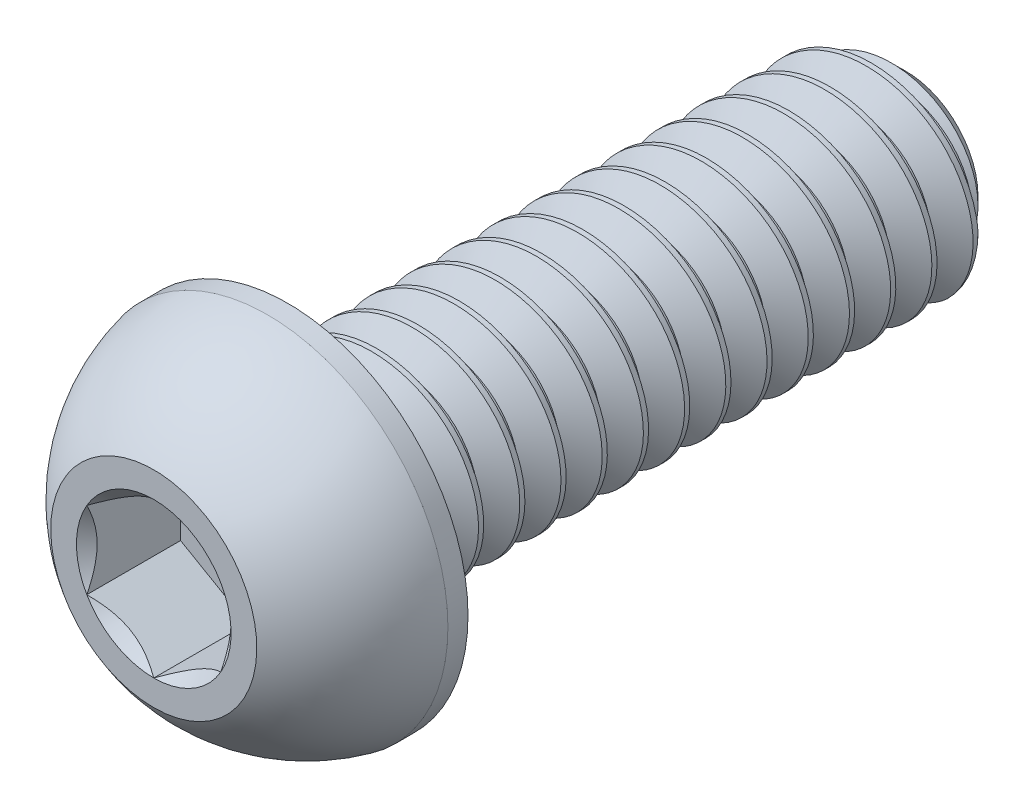
SolidWorks part; units mm, degrees
ref_plane "Front" through (0, 0, 0) normal (0, 0, 1) x (1, 0, 0)
ref_plane "Top" through (0, 0, 0) normal (0, 1, 0) x (1, 0, 0)
ref_plane "Right" through (0, 0, 0) normal (1, 0, 0) x (0, 0, -1)
sketch "Sketch1" plane through (0, 0, 0) normal (1, 0, 0) x (0, 0, -1)
  line L2 (1.3, 1) -> (7.3, 1)
  line L3 (7.3, 1) -> (7.3, 0)
  line L4 (7.3, 0) -> (1.3, 0)
  line L6 (1.105, 1.75) -> (1.3, 1.75) construction
  line L7 (7.3, 1) -> (7.3, -1) construction
  line L8 (0, 0) -> (1.3, 0) construction
  line L9 (1.3, 1.75) -> (1.3, -1.75) construction
  line L11 (1.3, 1) -> (1.3, 0)
  line L13 (0, 0.65) -> (0, -0.65) construction
  line L14 (0, 0.65) -> (0, 1) construction
  line L15 (7.275, 1.0433) -> (7.475, 0.6969) construction
  line L16 (7.475, 0.6969) -> (7.675, 1.0433) construction
  line L17 (7.675, 1.0433) -> (7.275, 1.0433) construction
  line L18 (7.3, 1) -> (7.65, 1) construction
  line L19 (7.475, 1.0433) -> (7.475, 1) construction
  line L20 (7.475, 1) -> (7.475, 0.7402) construction
  line L21 (7.475, 0.7402) -> (7.475, 0.6969) construction
  line L22 (7.45, 0.7402) -> (7.5, 0.7402)
  line L23 (7.2875, 1.0217) -> (7.6625, 1.0217)
  line L24 (7.5, 0.7402) -> (7.6625, 1.0217)
  line L25 (7.45, 0.7402) -> (7.2875, 1.0217)
  line L26 (7, 1) -> (7.3, 0.7)
  arc A3 (0, 1) -> (1.105, 1.75) centre (1.4858, 0) cw construction
  point P29 (7.475, 1.0217)
  point P30 (6.3, -1)
  dimension "D1" = 0.195
  dimension "Pitch" = 0.4
  dimension "D3" = 0.05
  dimension "D2" = 0.3
  dimension "D4" = 45
  dimension "D5" = 1
sketch "Sketch10" plane through (0, 0, 0) normal (1, 0, 0) x (0, 0, -1)
  line L0 (7, 1) -> (7.3, 0.7) construction
  line L1 (7, 1) -> (7.3, 0.7)
  line L4 (7.3, 1) -> (1.3, 1)
  line L5 (7.3, 0) -> (7.3, 1)
  line L6 (1.3, 0) -> (7.3, 0)
  line L7 (1.3, 1) -> (1.3, 0)
  line L8 (7, 1) -> (1.3, 1)
  line L9 (7.3, 0) -> (7.3, 0.7)
  line L10 (1.3, 0) -> (7.3, 0)
  line L11 (1.3, 1) -> (1.3, 0)
  dimension "D1" = 0
revolve "Revolve3" add sketch "Sketch10" angle 360 about L8
sketch "Sketch7" plane through (0, 0, 0) normal (1, 0, 0) x (0, 0, -1)
  line L6 (1.105, 1.75) -> (1.3, 1.75) construction
  line L8 (0, 0) -> (1.3, 0) construction
  line L11 (1.3, 1.75) -> (1.3, -1.75) construction
  line L12 (1.105, 1.75) -> (1.3, 1.75)
  line L13 (0, 0) -> (1.3, 0)
  line L14 (0, 0.65) -> (0, -0.65) construction
  line L15 (1.3, 1.75) -> (1.3, 0)
  line L16 (0, 1) -> (0, 0)
  arc A2 (1.105, 1.75) -> (0, 1) centre (1.4858, 0) ccw construction
  arc A3 (1.105, 1.75) -> (0, 1) centre (1.4858, 0) ccw
revolve "Revolve2" add sketch "Sketch7" angle 360 mid plane about L13
sketch "Sketch5" plane through (0, 0, 0) normal (0, 0, 1) x (1, 0, 0)
  line L1 (0.65, -0.3753) -> (0.65, 0.3753)
  line L2 (0.65, 0.3753) -> (0, 0.7506)
  line L3 (0, 0.7506) -> (-0.65, 0.3753)
  line L4 (-0.65, 0.3753) -> (-0.65, -0.3753)
  line L5 (-0.65, -0.3753) -> (0, -0.7506)
  line L6 (0, -0.7506) -> (0.65, -0.3753)
  circle A0 centre (0, 0) radius 0.65 construction
extrude "Cut-Extrude2" cut sketch "Sketch5" against normal blind 0.91
sketch "Sketch6" plane through (0, 0, 0) normal (0, 0, 1) x (1, 0, 0)
  circle A0 centre (0, 0) radius 0.7506
extrude "Cut-Extrude3" cut sketch "Sketch6" against normal blind 0.91 draft 45
sketch "Sketch9" plane through (0, 0, -1.3) normal (0, 0, -1) x (-1, 0, 0)
  circle A0 centre (0, 0) radius 1 construction
  circle A4 centre (0, 0) radius 1
split "Split1" bodies to split 113 resulting bodies 123 124 split by face at (1.75, 0, -1.3)
sketch "Sketch11" plane through (0, 0, -7.3) normal (0, 0, -1) x (-1, 0, 0)
  circle A0 centre (0, 0) radius 1 construction
  circle A1 centre (0, 0) radius 1
curve "Helix/Spiral1" pitch 0.4 height 7.3 radius 1 centre (0, 0, -7.3) axis (0, 0, 1) start towards (0, 1, 0)
sketch "Sketch12" plane through (0, 0, 0) normal (1, 0, 0) x (0, 0, -1)
  line L0 (7.45, 0.7402) -> (7.5, 0.7402) construction
  line L1 (7.5, 0.7402) -> (7.6625, 1.0217) construction
  line L2 (7.2875, 1.0217) -> (7.6625, 1.0217) construction
  line L3 (7.45, 0.7402) -> (7.2875, 1.0217) construction
  line L4 (7.45, 0.7402) -> (7.5, 0.7402)
  line L5 (7.5, 0.7402) -> (7.6625, 1.0217)
  line L6 (7.2875, 1.0217) -> (7.6625, 1.0217)
  line L7 (7.45, 0.7402) -> (7.2875, 1.0217)
sweep "Cut-Sweep2" cut profiles "Sketch12" path "Helix/Spiral1" align with end faces yes
extrude "Boss-Extrude1" add sketch "Sketch9" along normal blind 10 draft 45
equation "\"D1@Cut-Extrude2\" = \"Head Ht@Sketch1\" * .7"
equation "\"D1@Sketch1\" = \"Head Ht@Sketch1\" * .15"
equation "\"D1@Cut-Extrude3\" = \"D1@Cut-Extrude2\""
equation "\"D3@Sketch1\" = \"Pitch@Sketch1\" / 8"
equation "\"D2@Sketch1\"=\"Pitch@Sketch1\"*0.75"
equation "\"D3@Helix/Spiral1\" = \"Lg@Sketch1\" + \"Head Ht@Sketch1\""
equation "\"D4@Helix/Spiral1\"=\"pitch@sketch1\""
equation "\"D5@Sketch1\"=\"Pitch@Sketch1\"*2.5"
